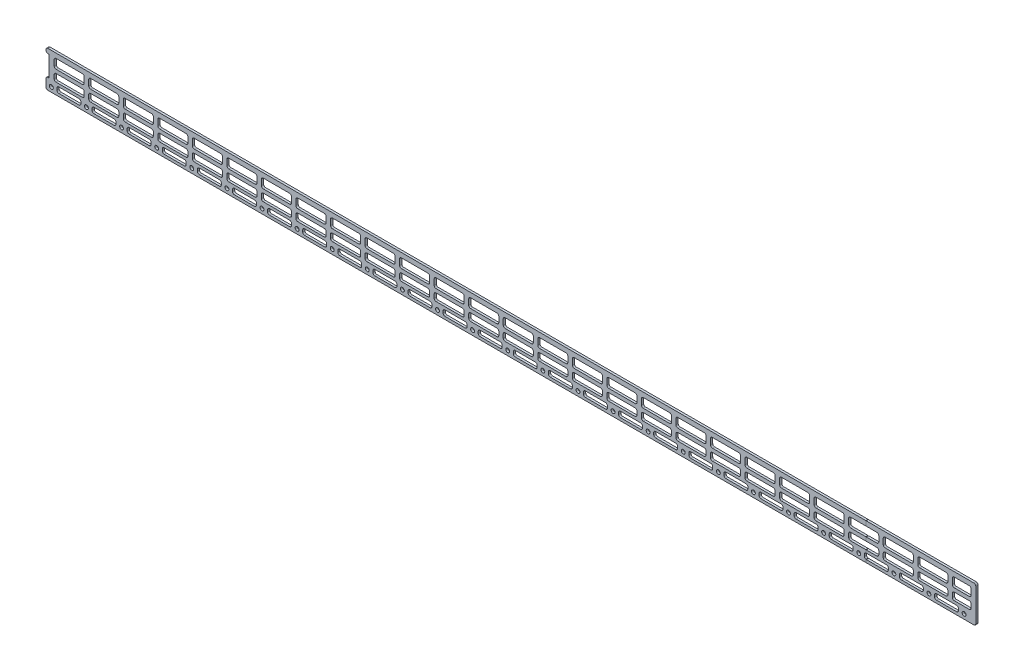
SolidWorks part; units mm, degrees
material "Thornel Mat VMA"
ref_plane "前视基准面" through (0, 0, 0) normal (0, 0, 1) x (1, 0, 0)
ref_plane "上视基准面" through (0, 0, 0) normal (0, 1, 0) x (1, 0, 0)
ref_plane "右视基准面" through (0, 0, 0) normal (1, 0, 0) x (0, 0, -1)
sketch "草图1" plane through (0, 0, 0) normal (0, 0, 1) x (1, 0, 0)
  line L0 (-244.2771, 4.75) -> (-222.1715, 4.75) construction
  line L1 (249.5, -9.75) -> (-249.5, -9.75)
  line L2 (249.5, -9.75) -> (249.5, 9.75)
  line L3 (249.5, 9.75) -> (-249.5, 9.75)
  line L4 (-249.5, -9.75) -> (-249.5, -3.75)
  line L5 (249.5, -9.75) -> (-249.5, 9.75) construction
  line L6 (249.5, 9.75) -> (-249.5, -9.75) construction
  line L12 (-228.98, -3.75) -> (-245.12, -3.75)
  line L13 (-245.12, -3.75) -> (-245.12, 0.25)
  line L14 (-245.12, 7.25) -> (-228.98, 7.25)
  line L15 (-228.98, 7.25) -> (-228.98, 2.25)
  line L124 (-211.94, -8.25) -> (-211.94, -5.25)
  line L125 (-230.78, -8.25) -> (-243.62, -8.25)
  line L126 (-230.78, -8.25) -> (-230.78, -5.25)
  line L127 (-230.78, -5.25) -> (-243.62, -5.25)
  line L128 (-243.62, -8.25) -> (-243.62, -5.25)
  line L129 (-230.78, -8.25) -> (-243.62, -5.25) construction
  line L130 (-230.78, -5.25) -> (-243.62, -8.25) construction
  line L131 (-211.94, -8.25) -> (-224.78, -8.25)
  line L132 (-224.78, -8.25) -> (-224.78, -5.25)
  line L133 (-211.94, -5.25) -> (-224.78, -5.25)
  line L134 (-193.1, -8.25) -> (-193.1, -5.25)
  line L135 (-193.1, -8.25) -> (-205.94, -8.25)
  line L136 (-205.94, -8.25) -> (-205.94, -5.25)
  line L137 (-193.1, -5.25) -> (-205.94, -5.25)
  line L138 (-174.26, -8.25) -> (-174.26, -5.25)
  line L139 (-174.26, -8.25) -> (-187.1, -8.25)
  line L140 (-187.1, -8.25) -> (-187.1, -5.25)
  line L141 (-174.26, -5.25) -> (-187.1, -5.25)
  line L142 (-155.42, -8.25) -> (-155.42, -5.25)
  line L143 (-155.42, -8.25) -> (-168.26, -8.25)
  line L144 (-168.26, -8.25) -> (-168.26, -5.25)
  line L145 (-155.42, -5.25) -> (-168.26, -5.25)
  line L146 (-136.58, -8.25) -> (-136.58, -5.25)
  line L147 (-136.58, -8.25) -> (-149.42, -8.25)
  line L148 (-149.42, -8.25) -> (-149.42, -5.25)
  line L149 (-136.58, -5.25) -> (-149.42, -5.25)
  line L150 (-117.74, -8.25) -> (-117.74, -5.25)
  line L151 (-117.74, -8.25) -> (-130.58, -8.25)
  line L152 (-130.58, -8.25) -> (-130.58, -5.25)
  line L153 (-117.74, -5.25) -> (-130.58, -5.25)
  line L154 (-98.9, -8.25) -> (-98.9, -5.25)
  line L155 (-98.9, -8.25) -> (-111.74, -8.25)
  line L156 (-111.74, -8.25) -> (-111.74, -5.25)
  line L157 (-98.9, -5.25) -> (-111.74, -5.25)
  line L158 (-80.06, -8.25) -> (-80.06, -5.25)
  line L159 (-80.06, -8.25) -> (-92.9, -8.25)
  line L160 (-92.9, -8.25) -> (-92.9, -5.25)
  line L161 (-80.06, -5.25) -> (-92.9, -5.25)
  line L162 (-61.22, -8.25) -> (-61.22, -5.25)
  line L163 (-61.22, -8.25) -> (-74.06, -8.25)
  line L164 (-74.06, -8.25) -> (-74.06, -5.25)
  line L165 (-61.22, -5.25) -> (-74.06, -5.25)
  line L166 (-42.38, -8.25) -> (-42.38, -5.25)
  line L167 (-42.38, -8.25) -> (-55.22, -8.25)
  line L168 (-55.22, -8.25) -> (-55.22, -5.25)
  line L169 (-42.38, -5.25) -> (-55.22, -5.25)
  line L170 (-23.54, -8.25) -> (-23.54, -5.25)
  line L171 (-23.54, -8.25) -> (-36.38, -8.25)
  line L172 (-36.38, -8.25) -> (-36.38, -5.25)
  line L173 (-23.54, -5.25) -> (-36.38, -5.25)
  line L174 (-4.7, -8.25) -> (-4.7, -5.25)
  line L175 (-4.7, -8.25) -> (-17.54, -8.25)
  line L176 (-17.54, -8.25) -> (-17.54, -5.25)
  line L177 (-4.7, -5.25) -> (-17.54, -5.25)
  line L178 (14.14, -8.25) -> (14.14, -5.25)
  line L179 (14.14, -8.25) -> (1.3, -8.25)
  line L180 (1.3, -8.25) -> (1.3, -5.25)
  line L181 (14.14, -5.25) -> (1.3, -5.25)
  line L182 (32.98, -8.25) -> (32.98, -5.25)
  line L183 (32.98, -8.25) -> (20.14, -8.25)
  line L184 (20.14, -8.25) -> (20.14, -5.25)
  line L185 (32.98, -5.25) -> (20.14, -5.25)
  line L186 (51.82, -8.25) -> (51.82, -5.25)
  line L187 (51.82, -8.25) -> (38.98, -8.25)
  line L188 (38.98, -8.25) -> (38.98, -5.25)
  line L189 (51.82, -5.25) -> (38.98, -5.25)
  line L190 (70.66, -8.25) -> (70.66, -5.25)
  line L191 (70.66, -8.25) -> (57.82, -8.25)
  line L192 (57.82, -8.25) -> (57.82, -5.25)
  line L193 (70.66, -5.25) -> (57.82, -5.25)
  line L194 (89.5, -8.25) -> (89.5, -5.25)
  line L195 (89.5, -8.25) -> (76.66, -8.25)
  line L196 (76.66, -8.25) -> (76.66, -5.25)
  line L197 (89.5, -5.25) -> (76.66, -5.25)
  line L198 (108.34, -8.25) -> (108.34, -5.25)
  line L199 (108.34, -8.25) -> (95.5, -8.25)
  line L200 (95.5, -8.25) -> (95.5, -5.25)
  line L201 (108.34, -5.25) -> (95.5, -5.25)
  line L202 (127.18, -8.25) -> (127.18, -5.25)
  line L203 (127.18, -8.25) -> (114.34, -8.25)
  line L204 (114.34, -8.25) -> (114.34, -5.25)
  line L205 (127.18, -5.25) -> (114.34, -5.25)
  line L206 (146.02, -8.25) -> (146.02, -5.25)
  line L207 (146.02, -8.25) -> (133.18, -8.25)
  line L208 (133.18, -8.25) -> (133.18, -5.25)
  line L209 (146.02, -5.25) -> (133.18, -5.25)
  line L210 (164.86, -8.25) -> (164.86, -5.25)
  line L211 (164.86, -8.25) -> (152.02, -8.25)
  line L212 (152.02, -8.25) -> (152.02, -5.25)
  line L213 (164.86, -5.25) -> (152.02, -5.25)
  line L214 (183.7, -8.25) -> (183.7, -5.25)
  line L215 (183.7, -8.25) -> (170.86, -8.25)
  line L216 (170.86, -8.25) -> (170.86, -5.25)
  line L217 (183.7, -5.25) -> (170.86, -5.25)
  line L218 (202.54, -8.25) -> (202.54, -5.25)
  line L219 (202.54, -8.25) -> (189.7, -8.25)
  line L220 (189.7, -8.25) -> (189.7, -5.25)
  line L221 (202.54, -5.25) -> (189.7, -5.25)
  line L222 (221.38, -8.25) -> (221.38, -5.25)
  line L223 (221.38, -8.25) -> (208.54, -8.25)
  line L224 (208.54, -8.25) -> (208.54, -5.25)
  line L225 (221.38, -5.25) -> (208.54, -5.25)
  line L226 (240.22, -8.25) -> (240.22, -5.25)
  line L227 (240.22, -8.25) -> (227.38, -8.25)
  line L228 (227.38, -8.25) -> (227.38, -5.25)
  line L229 (240.22, -5.25) -> (227.38, -5.25)
  line L230 (-249.5, 7.25) -> (-247.82, 7.25)
  line L231 (-247.82, 7.25) -> (-247.82, -3.75)
  line L232 (-247.82, -3.75) -> (-249.5, -3.75)
  line L233 (-249.5, 7.25) -> (-249.5, 9.75)
  line L238 (247, 7.25) -> (247, 2.25)
  line L239 (-245.12, 2.25) -> (-228.98, 2.25)
  line L240 (-245.12, 0.25) -> (-228.98, 0.25)
  line L241 (-245.12, 2.25) -> (-245.12, 7.25)
  line L242 (-228.98, 0.25) -> (-228.98, -3.75)
  line L243 (-226.58, 7.25) -> (-210.44, 7.25)
  line L244 (-210.44, 7.25) -> (-210.44, 2.25)
  line L245 (-226.58, 2.25) -> (-210.44, 2.25)
  line L246 (-226.58, 2.25) -> (-226.58, 7.25)
  line L247 (-210.44, -3.75) -> (-226.58, -3.75)
  line L248 (-226.58, -3.75) -> (-226.58, 0.25)
  line L249 (-226.58, 0.25) -> (-210.44, 0.25)
  line L250 (-210.44, 0.25) -> (-210.44, -3.75)
  line L251 (-208.04, 7.25) -> (-191.9, 7.25)
  line L252 (-191.9, 7.25) -> (-191.9, 2.25)
  line L253 (-208.04, 2.25) -> (-191.9, 2.25)
  line L254 (-208.04, 2.25) -> (-208.04, 7.25)
  line L255 (-191.9, -3.75) -> (-208.04, -3.75)
  line L256 (-208.04, -3.75) -> (-208.04, 0.25)
  line L257 (-208.04, 0.25) -> (-191.9, 0.25)
  line L258 (-191.9, 0.25) -> (-191.9, -3.75)
  line L259 (-189.5, 7.25) -> (-173.36, 7.25)
  line L260 (-173.36, 7.25) -> (-173.36, 2.25)
  line L261 (-189.5, 2.25) -> (-173.36, 2.25)
  line L262 (-189.5, 2.25) -> (-189.5, 7.25)
  line L263 (-173.36, -3.75) -> (-189.5, -3.75)
  line L264 (-189.5, -3.75) -> (-189.5, 0.25)
  line L265 (-189.5, 0.25) -> (-173.36, 0.25)
  line L266 (-173.36, 0.25) -> (-173.36, -3.75)
  line L267 (-170.96, 7.25) -> (-154.82, 7.25)
  line L268 (-154.82, 7.25) -> (-154.82, 2.25)
  line L269 (-170.96, 2.25) -> (-154.82, 2.25)
  line L270 (-170.96, 2.25) -> (-170.96, 7.25)
  line L271 (-154.82, -3.75) -> (-170.96, -3.75)
  line L272 (-170.96, -3.75) -> (-170.96, 0.25)
  line L273 (-170.96, 0.25) -> (-154.82, 0.25)
  line L274 (-154.82, 0.25) -> (-154.82, -3.75)
  line L275 (-152.42, 7.25) -> (-136.28, 7.25)
  line L276 (-136.28, 7.25) -> (-136.28, 2.25)
  line L277 (-152.42, 2.25) -> (-136.28, 2.25)
  line L278 (-152.42, 2.25) -> (-152.42, 7.25)
  line L279 (-136.28, -3.75) -> (-152.42, -3.75)
  line L280 (-152.42, -3.75) -> (-152.42, 0.25)
  line L281 (-152.42, 0.25) -> (-136.28, 0.25)
  line L282 (-136.28, 0.25) -> (-136.28, -3.75)
  line L283 (-133.88, 7.25) -> (-117.74, 7.25)
  line L284 (-117.74, 7.25) -> (-117.74, 2.25)
  line L285 (-133.88, 2.25) -> (-117.74, 2.25)
  line L286 (-133.88, 2.25) -> (-133.88, 7.25)
  line L287 (-117.74, -3.75) -> (-133.88, -3.75)
  line L288 (-133.88, -3.75) -> (-133.88, 0.25)
  line L289 (-133.88, 0.25) -> (-117.74, 0.25)
  line L290 (-117.74, 0.25) -> (-117.74, -3.75)
  line L291 (-115.34, 7.25) -> (-99.2, 7.25)
  line L292 (-99.2, 7.25) -> (-99.2, 2.25)
  line L293 (-115.34, 2.25) -> (-99.2, 2.25)
  line L294 (-115.34, 2.25) -> (-115.34, 7.25)
  line L295 (-99.2, -3.75) -> (-115.34, -3.75)
  line L296 (-115.34, -3.75) -> (-115.34, 0.25)
  line L297 (-115.34, 0.25) -> (-99.2, 0.25)
  line L298 (-99.2, 0.25) -> (-99.2, -3.75)
  line L299 (-96.8, 7.25) -> (-80.66, 7.25)
  line L300 (-80.66, 7.25) -> (-80.66, 2.25)
  line L301 (-96.8, 2.25) -> (-80.66, 2.25)
  line L302 (-96.8, 2.25) -> (-96.8, 7.25)
  line L303 (-80.66, -3.75) -> (-96.8, -3.75)
  line L304 (-96.8, -3.75) -> (-96.8, 0.25)
  line L305 (-96.8, 0.25) -> (-80.66, 0.25)
  line L306 (-80.66, 0.25) -> (-80.66, -3.75)
  line L307 (-78.26, 7.25) -> (-62.12, 7.25)
  line L308 (-62.12, 7.25) -> (-62.12, 2.25)
  line L309 (-78.26, 2.25) -> (-62.12, 2.25)
  line L310 (-78.26, 2.25) -> (-78.26, 7.25)
  line L311 (-62.12, -3.75) -> (-78.26, -3.75)
  line L312 (-78.26, -3.75) -> (-78.26, 0.25)
  line L313 (-78.26, 0.25) -> (-62.12, 0.25)
  line L314 (-62.12, 0.25) -> (-62.12, -3.75)
  line L315 (-59.72, 7.25) -> (-43.58, 7.25)
  line L316 (-43.58, 7.25) -> (-43.58, 2.25)
  line L317 (-59.72, 2.25) -> (-43.58, 2.25)
  line L318 (-59.72, 2.25) -> (-59.72, 7.25)
  line L319 (-43.58, -3.75) -> (-59.72, -3.75)
  line L320 (-59.72, -3.75) -> (-59.72, 0.25)
  line L321 (-59.72, 0.25) -> (-43.58, 0.25)
  line L322 (-43.58, 0.25) -> (-43.58, -3.75)
  line L323 (-41.18, 7.25) -> (-25.04, 7.25)
  line L324 (-25.04, 7.25) -> (-25.04, 2.25)
  line L325 (-41.18, 2.25) -> (-25.04, 2.25)
  line L326 (-41.18, 2.25) -> (-41.18, 7.25)
  line L327 (-25.04, -3.75) -> (-41.18, -3.75)
  line L328 (-41.18, -3.75) -> (-41.18, 0.25)
  line L329 (-41.18, 0.25) -> (-25.04, 0.25)
  line L330 (-25.04, 0.25) -> (-25.04, -3.75)
  line L331 (-22.64, 7.25) -> (-6.5, 7.25)
  line L332 (-6.5, 7.25) -> (-6.5, 2.25)
  line L333 (-22.64, 2.25) -> (-6.5, 2.25)
  line L334 (-22.64, 2.25) -> (-22.64, 7.25)
  line L335 (-6.5, -3.75) -> (-22.64, -3.75)
  line L336 (-22.64, -3.75) -> (-22.64, 0.25)
  line L337 (-22.64, 0.25) -> (-6.5, 0.25)
  line L338 (-6.5, 0.25) -> (-6.5, -3.75)
  line L339 (-4.1, 7.25) -> (12.04, 7.25)
  line L340 (12.04, 7.25) -> (12.04, 2.25)
  line L341 (-4.1, 2.25) -> (12.04, 2.25)
  line L342 (-4.1, 2.25) -> (-4.1, 7.25)
  line L343 (12.04, -3.75) -> (-4.1, -3.75)
  line L344 (-4.1, -3.75) -> (-4.1, 0.25)
  line L345 (-4.1, 0.25) -> (12.04, 0.25)
  line L346 (12.04, 0.25) -> (12.04, -3.75)
  line L347 (14.44, 7.25) -> (30.58, 7.25)
  line L348 (30.58, 7.25) -> (30.58, 2.25)
  line L349 (14.44, 2.25) -> (30.58, 2.25)
  line L350 (14.44, 2.25) -> (14.44, 7.25)
  line L351 (30.58, -3.75) -> (14.44, -3.75)
  line L352 (14.44, -3.75) -> (14.44, 0.25)
  line L353 (14.44, 0.25) -> (30.58, 0.25)
  line L354 (30.58, 0.25) -> (30.58, -3.75)
  line L355 (32.98, 7.25) -> (49.12, 7.25)
  line L356 (49.12, 7.25) -> (49.12, 2.25)
  line L357 (32.98, 2.25) -> (49.12, 2.25)
  line L358 (32.98, 2.25) -> (32.98, 7.25)
  line L359 (49.12, -3.75) -> (32.98, -3.75)
  line L360 (32.98, -3.75) -> (32.98, 0.25)
  line L361 (32.98, 0.25) -> (49.12, 0.25)
  line L362 (49.12, 0.25) -> (49.12, -3.75)
  line L363 (51.52, 7.25) -> (67.66, 7.25)
  line L364 (67.66, 7.25) -> (67.66, 2.25)
  line L365 (51.52, 2.25) -> (67.66, 2.25)
  line L366 (51.52, 2.25) -> (51.52, 7.25)
  line L367 (67.66, -3.75) -> (51.52, -3.75)
  line L368 (51.52, -3.75) -> (51.52, 0.25)
  line L369 (51.52, 0.25) -> (67.66, 0.25)
  line L370 (67.66, 0.25) -> (67.66, -3.75)
  line L371 (70.06, 7.25) -> (86.2, 7.25)
  line L372 (86.2, 7.25) -> (86.2, 2.25)
  line L373 (70.06, 2.25) -> (86.2, 2.25)
  line L374 (70.06, 2.25) -> (70.06, 7.25)
  line L375 (86.2, -3.75) -> (70.06, -3.75)
  line L376 (70.06, -3.75) -> (70.06, 0.25)
  line L377 (70.06, 0.25) -> (86.2, 0.25)
  line L378 (86.2, 0.25) -> (86.2, -3.75)
  line L379 (88.6, 7.25) -> (104.74, 7.25)
  line L380 (104.74, 7.25) -> (104.74, 2.25)
  line L381 (88.6, 2.25) -> (104.74, 2.25)
  line L382 (88.6, 2.25) -> (88.6, 7.25)
  line L383 (104.74, -3.75) -> (88.6, -3.75)
  line L384 (88.6, -3.75) -> (88.6, 0.25)
  line L385 (88.6, 0.25) -> (104.74, 0.25)
  line L386 (104.74, 0.25) -> (104.74, -3.75)
  line L387 (107.14, 7.25) -> (123.28, 7.25)
  line L388 (123.28, 7.25) -> (123.28, 2.25)
  line L389 (107.14, 2.25) -> (123.28, 2.25)
  line L390 (107.14, 2.25) -> (107.14, 7.25)
  line L391 (123.28, -3.75) -> (107.14, -3.75)
  line L392 (107.14, -3.75) -> (107.14, 0.25)
  line L393 (107.14, 0.25) -> (123.28, 0.25)
  line L394 (123.28, 0.25) -> (123.28, -3.75)
  line L395 (125.68, 7.25) -> (141.82, 7.25)
  line L396 (141.82, 7.25) -> (141.82, 2.25)
  line L397 (125.68, 2.25) -> (141.82, 2.25)
  line L398 (125.68, 2.25) -> (125.68, 7.25)
  line L399 (141.82, -3.75) -> (125.68, -3.75)
  line L400 (125.68, -3.75) -> (125.68, 0.25)
  line L401 (125.68, 0.25) -> (141.82, 0.25)
  line L402 (141.82, 0.25) -> (141.82, -3.75)
  line L403 (144.22, 7.25) -> (160.36, 7.25)
  line L404 (160.36, 7.25) -> (160.36, 2.25)
  line L405 (144.22, 2.25) -> (160.36, 2.25)
  line L406 (144.22, 2.25) -> (144.22, 7.25)
  line L407 (160.36, -3.75) -> (144.22, -3.75)
  line L408 (144.22, -3.75) -> (144.22, 0.25)
  line L409 (144.22, 0.25) -> (160.36, 0.25)
  line L410 (160.36, 0.25) -> (160.36, -3.75)
  line L411 (162.76, 7.25) -> (178.9, 7.25)
  line L412 (178.9, 7.25) -> (178.9, 2.25)
  line L413 (162.76, 2.25) -> (178.9, 2.25)
  line L414 (162.76, 2.25) -> (162.76, 7.25)
  line L415 (178.9, -3.75) -> (162.76, -3.75)
  line L416 (162.76, -3.75) -> (162.76, 0.25)
  line L417 (162.76, 0.25) -> (178.9, 0.25)
  line L418 (178.9, 0.25) -> (178.9, -3.75)
  line L419 (181.3, 7.25) -> (197.44, 7.25)
  line L420 (197.44, 7.25) -> (197.44, 2.25)
  line L421 (181.3, 2.25) -> (197.44, 2.25)
  line L422 (181.3, 2.25) -> (181.3, 7.25)
  line L423 (197.44, -3.75) -> (181.3, -3.75)
  line L424 (181.3, -3.75) -> (181.3, 0.25)
  line L425 (181.3, 0.25) -> (197.44, 0.25)
  line L426 (197.44, 0.25) -> (197.44, -3.75)
  line L427 (199.84, 7.25) -> (215.98, 7.25)
  line L428 (215.98, 7.25) -> (215.98, 2.25)
  line L429 (199.84, 2.25) -> (215.98, 2.25)
  line L430 (199.84, 2.25) -> (199.84, 7.25)
  line L431 (215.98, -3.75) -> (199.84, -3.75)
  line L432 (199.84, -3.75) -> (199.84, 0.25)
  line L433 (199.84, 0.25) -> (215.98, 0.25)
  line L434 (215.98, 0.25) -> (215.98, -3.75)
  line L435 (218.38, 7.25) -> (234.52, 7.25)
  line L436 (234.52, 7.25) -> (234.52, 2.25)
  line L437 (218.38, 2.25) -> (234.52, 2.25)
  line L438 (218.38, 2.25) -> (218.38, 7.25)
  line L439 (234.52, -3.75) -> (218.38, -3.75)
  line L440 (218.38, -3.75) -> (218.38, 0.25)
  line L441 (218.38, 0.25) -> (234.52, 0.25)
  line L442 (234.52, 0.25) -> (234.52, -3.75)
  line L443 (236.92, 7.25) -> (247, 7.25)
  line L445 (236.92, 2.25) -> (247, 2.25)
  line L446 (236.92, 2.25) -> (236.92, 7.25)
  line L447 (247, -3.75) -> (236.92, -3.75)
  line L448 (236.92, -3.75) -> (236.92, 0.25)
  line L449 (236.92, 0.25) -> (247, 0.25)
  line L451 (253.06, 7.25) -> (253.06, 2.25) [skipped]
  line L452 (253.06, 0.25) -> (253.06, -3.75) [skipped]
  line L453 (247, 0.25) -> (247, -3.75)
  circle A0 centre (-246.62, -7.25) radius 1.05
  circle A1 centre (-227.78, -7.25) radius 1.05
  circle A2 centre (-208.94, -7.25) radius 1.05
  circle A3 centre (-190.1, -7.25) radius 1.05
  circle A4 centre (-171.26, -7.25) radius 1.05
  circle A5 centre (-152.42, -7.25) radius 1.05
  circle A6 centre (-133.58, -7.25) radius 1.05
  circle A7 centre (-114.74, -7.25) radius 1.05
  circle A8 centre (-95.9, -7.25) radius 1.05
  circle A9 centre (-77.06, -7.25) radius 1.05
  circle A10 centre (-58.22, -7.25) radius 1.05
  circle A11 centre (-39.38, -7.25) radius 1.05
  circle A12 centre (-20.54, -7.25) radius 1.05
  circle A13 centre (-1.7, -7.25) radius 1.05
  circle A14 centre (17.14, -7.25) radius 1.05
  circle A15 centre (35.98, -7.25) radius 1.05
  circle A16 centre (54.82, -7.25) radius 1.05
  circle A17 centre (73.66, -7.25) radius 1.05
  circle A18 centre (92.5, -7.25) radius 1.05
  circle A19 centre (111.34, -7.25) radius 1.05
  circle A20 centre (130.18, -7.25) radius 1.05
  circle A21 centre (149.02, -7.25) radius 1.05
  circle A22 centre (167.86, -7.25) radius 1.05
  circle A23 centre (186.7, -7.25) radius 1.05
  circle A24 centre (205.54, -7.25) radius 1.05
  circle A25 centre (224.38, -7.25) radius 1.05
  circle A26 centre (243.22, -7.25) radius 1.05
  point P0 (0, 0)
  point P62 (-237.2, -6.75)
  point P171 (-237.2, -8.25)
  dimension "D3" = 2.1
  dimension "D7" = 18.84
  dimension "D10" = 27
  dimension "D14" = 1.2
  dimension "D1" = 499
  dimension "D2" = 5
  dimension "D4" = 2.5
  dimension "D5" = 2.88
  dimension "D8" = 12
  dimension "D9" = 6
  dimension "D11" = 1.5
  dimension "D12" = 1.2
  dimension "D13" = 2.5
  dimension "D15" = 1.5
  dimension "D16" = 1.5
  dimension "D17" = 3
  dimension "D18" = 3
  dimension "D20" = 3
  dimension "D21" = 1.2
  dimension "D22" = 2.5
  dimension "D23" = 2
  dimension "D24" = 4
  dimension "D6" = 27
  dimension "D19" = 26
extrude "凸台-拉伸1" add sketch "草图1" along normal blind 1.2
fillet "圆角1" radius 1 326 edges at (141.82, -3.75, 0.6) (141.82, 0.25, 0.6) (125.68, 0.25, 0.6) (125.68, -3.75, 0.6) (125.68, 7.25, 0.6) (125.68, 2.25, 0.6) (141.82, 2.25, 0.6) (141.82, 7.25, 0.6) (160.36, -3.75, 0.6) (160.36, 0.25, 0.6) (144.22, 0.25, 0.6) (144.22, -3.75, 0.6) (144.22, 7.25, 0.6) (144.22, 2.25, 0.6) (160.36, 2.25, 0.6) (160.36, 7.25, 0.6) (178.9, -3.75, 0.6) (178.9, 0.25, 0.6) (162.76, 0.25, 0.6) (162.76, -3.75, 0.6) (162.76, 7.25, 0.6) (162.76, 2.25, 0.6) (178.9, 2.25, 0.6) (178.9, 7.25, 0.6) (197.44, -3.75, 0.6) (197.44, 0.25, 0.6) (181.3, 0.25, 0.6) (181.3, -3.75, 0.6) (181.3, 7.25, 0.6) (181.3, 2.25, 0.6) (197.44, 2.25, 0.6) (197.44, 7.25, 0.6) (215.98, -3.75, 0.6) (215.98, 0.25, 0.6) (199.84, 0.25, 0.6) (199.84, -3.75, 0.6) (199.84, 7.25, 0.6) (199.84, 2.25, 0.6) (215.98, 2.25, 0.6) (215.98, 7.25, 0.6) (234.52, -3.75, 0.6) (234.52, 0.25, 0.6) (218.38, 0.25, 0.6) (218.38, -3.75, 0.6) (218.38, 7.25, 0.6) (218.38, 2.25, 0.6) (234.52, 2.25, 0.6) (234.52, 7.25, 0.6) (-228.98, -3.75, 0.6) (-228.98, 0.25, 0.6) (-245.12, 0.25, 0.6) (-245.12, -3.75, 0.6) (-249.5, 9.75, 0.6) (249.5, 9.75, 0.6) (249.5, -9.75, 0.6) (-249.5, -9.75, 0.6) (-249.5, -3.75, 0.6) (-191.9, -3.75, 0.6) (-191.9, 0.25, 0.6) (-208.04, 0.25, 0.6) (-208.04, -3.75, 0.6) (-249.5, 7.25, 0.6) (-243.62, -5.25, 0.6) (-243.62, -8.25, 0.6) (-230.78, -8.25, 0.6) (-230.78, -5.25, 0.6) (-245.12, 7.25, 0.6) (-245.12, 2.25, 0.6) (-228.98, 2.25, 0.6) (-228.98, 7.25, 0.6) (-210.44, -3.75, 0.6) (-210.44, 0.25, 0.6) (-226.58, 0.25, 0.6) (-226.58, -3.75, 0.6) (-226.58, 7.25, 0.6) (-226.58, 2.25, 0.6) (-210.44, 2.25, 0.6) (-210.44, 7.25, 0.6) (-208.04, 7.25, 0.6) (-208.04, 2.25, 0.6) (-191.9, 2.25, 0.6) (-191.9, 7.25, 0.6) (-173.36, -3.75, 0.6) (-173.36, 0.25, 0.6) (-189.5, 0.25, 0.6) (-189.5, -3.75, 0.6) (-189.5, 7.25, 0.6) (-189.5, 2.25, 0.6) (-173.36, 2.25, 0.6) (-173.36, 7.25, 0.6) (-154.82, -3.75, 0.6) (-154.82, 0.25, 0.6) (-170.96, 0.25, 0.6) (-170.96, -3.75, 0.6) (-170.96, 7.25, 0.6) (-170.96, 2.25, 0.6) (-154.82, 2.25, 0.6) (-154.82, 7.25, 0.6) (-136.28, -3.75, 0.6) (-136.28, 0.25, 0.6) (-152.42, 0.25, 0.6) (-152.42, -3.75, 0.6) (-152.42, 7.25, 0.6) (-152.42, 2.25, 0.6) (-136.28, 2.25, 0.6) (-136.28, 7.25, 0.6) (-117.74, -3.75, 0.6) (-117.74, 0.25, 0.6) (-133.88, 0.25, 0.6) (-133.88, -3.75, 0.6) (-133.88, 7.25, 0.6) (-133.88, 2.25, 0.6) (-117.74, 2.25, 0.6) (-117.74, 7.25, 0.6) (-99.2, -3.75, 0.6) (-99.2, 0.25, 0.6) (-115.34, 0.25, 0.6) (-115.34, -3.75, 0.6) (-115.34, 7.25, 0.6) (-115.34, 2.25, 0.6) (-99.2, 2.25, 0.6) (-99.2, 7.25, 0.6) (-80.66, -3.75, 0.6) (-80.66, 0.25, 0.6) (-96.8, 0.25, 0.6) (-96.8, -3.75, 0.6) (-96.8, 7.25, 0.6) (-96.8, 2.25, 0.6) (-80.66, 2.25, 0.6) (-80.66, 7.25, 0.6) (-62.12, -3.75, 0.6) (-62.12, 0.25, 0.6) (-78.26, 0.25, 0.6) (-78.26, -3.75, 0.6) (-78.26, 7.25, 0.6) (-78.26, 2.25, 0.6) (-62.12, 2.25, 0.6) (-62.12, 7.25, 0.6) (-43.58, -3.75, 0.6) (-43.58, 0.25, 0.6) (-59.72, 0.25, 0.6) (-59.72, -3.75, 0.6) (-59.72, 7.25, 0.6) (-59.72, 2.25, 0.6) (-43.58, 2.25, 0.6) (-43.58, 7.25, 0.6) (-25.04, -3.75, 0.6) (-25.04, 0.25, 0.6) (-41.18, 0.25, 0.6) (-41.18, -3.75, 0.6) (-41.18, 7.25, 0.6) (-41.18, 2.25, 0.6) (-25.04, 2.25, 0.6) (-25.04, 7.25, 0.6) (-6.5, -3.75, 0.6) (-6.5, 0.25, 0.6) (-22.64, 0.25, 0.6) (-22.64, -3.75, 0.6) (-22.64, 7.25, 0.6) (-22.64, 2.25, 0.6) (-6.5, 2.25, 0.6) (-6.5, 7.25, 0.6) (-211.94, -5.25, 0.6) (-224.78, -5.25, 0.6) (-224.78, -8.25, 0.6) (-211.94, -8.25, 0.6) (-193.1, -5.25, 0.6) (-205.94, -5.25, 0.6) (-205.94, -8.25, 0.6) (-193.1, -8.25, 0.6) (-174.26, -5.25, 0.6) (-187.1, -5.25, 0.6) (-187.1, -8.25, 0.6) (-174.26, -8.25, 0.6) (-155.42, -5.25, 0.6) (-168.26, -5.25, 0.6) (-168.26, -8.25, 0.6) (-155.42, -8.25, 0.6) (-136.58, -5.25, 0.6) (-149.42, -5.25, 0.6) (-149.42, -8.25, 0.6) (-136.58, -8.25, 0.6) (-117.74, -5.25, 0.6) (-130.58, -5.25, 0.6) (-130.58, -8.25, 0.6) (-117.74, -8.25, 0.6) (-98.9, -5.25, 0.6) (-111.74, -5.25, 0.6) (-111.74, -8.25, 0.6) (-98.9, -8.25, 0.6) (-80.06, -5.25, 0.6) (-92.9, -5.25, 0.6) (-92.9, -8.25, 0.6) (-80.06, -8.25, 0.6) (-61.22, -5.25, 0.6) (-74.06, -5.25, 0.6) (-74.06, -8.25, 0.6) (-61.22, -8.25, 0.6) (-42.38, -5.25, 0.6) (-55.22, -5.25, 0.6) (-55.22, -8.25, 0.6) (-42.38, -8.25, 0.6) (-23.54, -5.25, 0.6) (-36.38, -5.25, 0.6) (-36.38, -8.25, 0.6) (-23.54, -8.25, 0.6) (-4.7, -5.25, 0.6) (-17.54, -5.25, 0.6) (-17.54, -8.25, 0.6) (-4.7, -8.25, 0.6) (14.14, -5.25, 0.6) (1.3, -5.25, 0.6) (1.3, -8.25, 0.6) (14.14, -8.25, 0.6) (32.98, -5.25, 0.6) (20.14, -5.25, 0.6) (20.14, -8.25, 0.6) (32.98, -8.25, 0.6) (51.82, -5.25, 0.6) (38.98, -5.25, 0.6) (38.98, -8.25, 0.6) (51.82, -8.25, 0.6) (70.66, -5.25, 0.6) (57.82, -5.25, 0.6) (57.82, -8.25, 0.6) (70.66, -8.25, 0.6) (89.5, -5.25, 0.6) (76.66, -5.25, 0.6) (76.66, -8.25, 0.6) (89.5, -8.25, 0.6) (108.34, -5.25, 0.6) (95.5, -5.25, 0.6) (95.5, -8.25, 0.6) (108.34, -8.25, 0.6) (127.18, -5.25, 0.6) (114.34, -5.25, 0.6) (114.34, -8.25, 0.6) (127.18, -8.25, 0.6) (146.02, -5.25, 0.6) (133.18, -5.25, 0.6) (133.18, -8.25, 0.6) (146.02, -8.25, 0.6) (164.86, -5.25, 0.6) (152.02, -5.25, 0.6) (152.02, -8.25, 0.6) (164.86, -8.25, 0.6) (183.7, -5.25, 0.6) (170.86, -5.25, 0.6) (170.86, -8.25, 0.6) (183.7, -8.25, 0.6) (202.54, -5.25, 0.6) (189.7, -5.25, 0.6) (189.7, -8.25, 0.6) (202.54, -8.25, 0.6) (221.38, -5.25, 0.6) (208.54, -5.25, 0.6) (208.54, -8.25, 0.6) (221.38, -8.25, 0.6) (240.22, -5.25, 0.6) (227.38, -5.25, 0.6) (227.38, -8.25, 0.6) (240.22, -8.25, 0.6) (12.04, -3.75, 0.6) (12.04, 0.25, 0.6) (-4.1, 0.25, 0.6) (-4.1, -3.75, 0.6) (-4.1, 7.25, 0.6) (-4.1, 2.25, 0.6) (12.04, 2.25, 0.6) (12.04, 7.25, 0.6) (247, 7.25, 0.6) (236.92, 7.25, 0.6) (236.92, 2.25, 0.6) (247, 2.25, 0.6) (247, -3.75, 0.6) (247, 0.25, 0.6) (236.92, 0.25, 0.6) (236.92, -3.75, 0.6) (30.58, -3.75, 0.6) (30.58, 0.25, 0.6) (14.44, 0.25, 0.6) (14.44, -3.75, 0.6) (14.44, 7.25, 0.6) (14.44, 2.25, 0.6) (30.58, 2.25, 0.6) (30.58, 7.25, 0.6) (49.12, -3.75, 0.6) (49.12, 0.25, 0.6) (32.98, 0.25, 0.6) (32.98, -3.75, 0.6) (32.98, 7.25, 0.6) (32.98, 2.25, 0.6) (49.12, 2.25, 0.6) (49.12, 7.25, 0.6) (67.66, -3.75, 0.6) (67.66, 0.25, 0.6) (51.52, 0.25, 0.6) (51.52, -3.75, 0.6) (51.52, 7.25, 0.6) (51.52, 2.25, 0.6) (67.66, 2.25, 0.6) (67.66, 7.25, 0.6) (86.2, -3.75, 0.6) (86.2, 0.25, 0.6) (70.06, 0.25, 0.6) (70.06, -3.75, 0.6) (70.06, 7.25, 0.6) (70.06, 2.25, 0.6) (86.2, 2.25, 0.6) (86.2, 7.25, 0.6) (104.74, -3.75, 0.6) (104.74, 0.25, 0.6) (88.6, 0.25, 0.6) (88.6, -3.75, 0.6) (88.6, 7.25, 0.6) (88.6, 2.25, 0.6) (104.74, 2.25, 0.6) (104.74, 7.25, 0.6) (123.28, -3.75, 0.6) (123.28, 0.25, 0.6) (107.14, 0.25, 0.6) (107.14, -3.75, 0.6) (107.14, 7.25, 0.6) (107.14, 2.25, 0.6) (123.28, 2.25, 0.6) (123.28, 7.25, 0.6)
sketch "草图2" plane through (0, 0, 1.2) normal (0, 0, 1) x (1, 0, 0)
  line L0 (-249.5, -4.75) -> (-249.5, -8.75) construction
  line L1 (190.7, -11.0961) -> (190.5, -11.0961)
  line L2 (190.7, -11.0961) -> (190.7, 19.3925)
  line L3 (190.7, 19.3925) -> (190.5, 19.3925)
  line L4 (190.5, -11.0961) -> (190.5, 19.3925)
  line L5 (190.7, -11.0961) -> (190.5, 19.3925) construction
  line L6 (190.7, 19.3925) -> (190.5, -11.0961) construction
  point P0 (190.6, 4.1482)
  dimension "D1" = 440
  dimension "D2" = 0.2
extrude "切除-拉伸1" cut sketch "草图2" against normal blind 10
